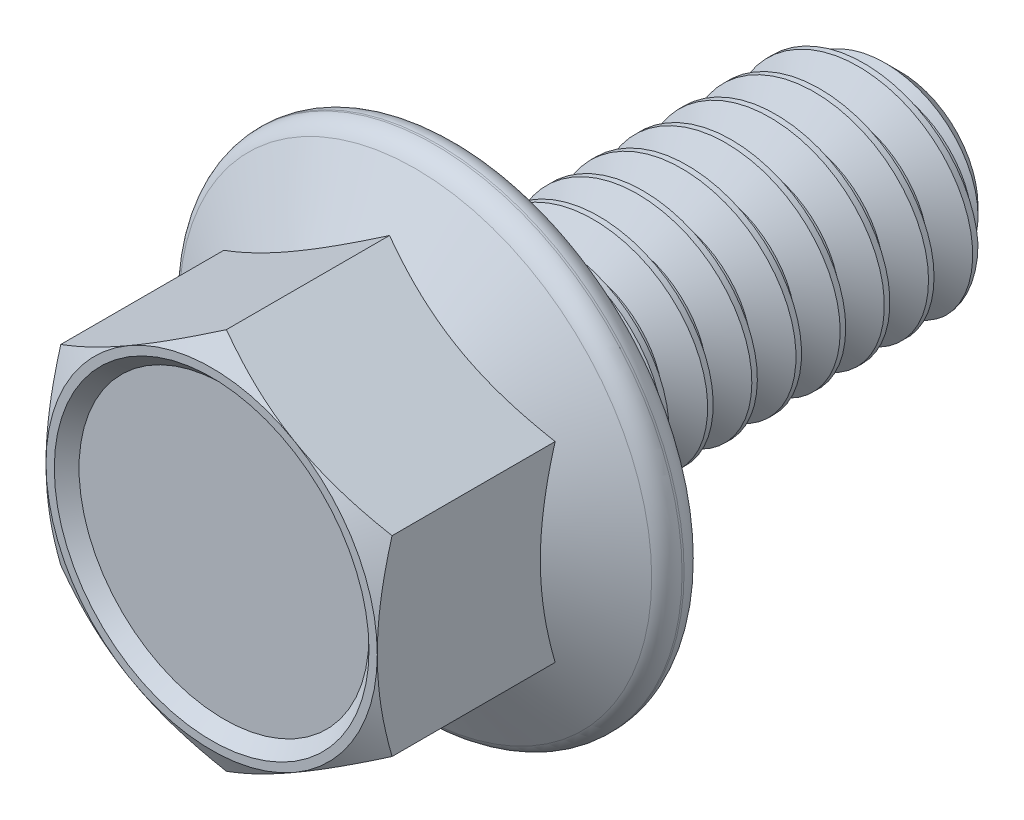
SolidWorks part; units mm, degrees
ref_plane "Front Plane" through (0, 0, 0) normal (0, 0, 1) x (1, 0, 0)
ref_plane "Top Plane" through (0, 0, 0) normal (0, 1, 0) x (1, 0, 0)
ref_plane "Right Plane" through (0, 0, 0) normal (1, 0, 0) x (0, 0, -1)
sketch "Sketch1" plane through (0, 0, 0) normal (1, 0, 0) x (0, 0, -1)
  line L0 (-9.906, 0) -> (9.906, 0) construction
  line L1 (9.8266, 3.3125) -> (10.4616, 2.2126) construction
  line L2 (10.4616, 2.2126) -> (11.0966, 3.3125) construction
  line L3 (11.0966, 3.3125) -> (9.8266, 3.3125) construction
  line L4 (9.906, 0) -> (9.906, 2.2225)
  line L5 (9.906, 2.2225) -> (8.9535, 3.175)
  line L6 (8.9535, 3.175) -> (-2.794, 3.175)
  line L7 (-2.794, 3.175) -> (-2.794, 7.112)
  line L8 (-2.794, 7.112) -> (-3.8608, 7.112)
  line L9 (8.9535, -3.175) -> (9.906, -2.2225) construction
  line L10 (-5.2173, 4.7625) -> (-9.906, 4.7625)
  line L11 (-9.906, 4.7625) -> (-9.906, 0)
  line L12 (8.9535, 3.175) -> (9.906, 3.175) construction
  line L13 (9.906, 3.175) -> (9.906, 2.2225) construction
  line L14 (10.4616, 2.2126) -> (10.4616, 2.3501) construction
  line L15 (-3.8608, 7.112) -> (-5.2173, 4.7625)
  line L16 (10.4616, 3.175) -> (10.4616, 3.3125) construction
  line L17 (9.8663, 3.2437) -> (11.0569, 3.2437) construction
  line L19 (11.0172, 3.175) -> (9.906, 3.175) construction
  line L21 (10.3822, 2.3501) -> (10.541, 2.3501) construction
  point P12 (6.731, 3.175)
  point P14 (10.4616, 3.2437)
  point P19 (6.731, -3.175)
  dimension "Screw Size Decimal Equivalent" = 6.35
  dimension "Flange Diameter" = 14.224
  dimension "Head Width" = 9.525
  dimension "Thread Pitch" = 1.27
  dimension "D1" = 0.1588
  dimension "D2" = 0.9525
  dimension "Length" = 12.7
  dimension "Head Height" = 7.112
  dimension "D3" = 1.0668
  dimension "D4" = 60
  dimension "D5" = 3.175
  dimension "Thread Size" = 6.35
sketch "Sketch2" plane through (0, 0, 0) normal (1, 0, 0) x (0, 0, -1)
  line L0 (-9.906, 0) -> (9.906, 0) construction
  line L1 (9.906, 0) -> (9.906, 2.2225) construction
  line L2 (9.906, 2.2225) -> (8.9535, 3.175) construction
  line L3 (8.9535, 3.175) -> (-2.794, 3.175) construction
  line L4 (-2.794, 3.175) -> (-2.794, 7.112) construction
  line L5 (-2.794, 7.112) -> (-3.8608, 7.112) construction
  line L6 (-3.8608, 7.112) -> (-5.2173, 4.7625) construction
  line L7 (-5.2173, 4.7625) -> (-9.906, 4.7625) construction
  line L8 (-9.906, 4.7625) -> (-9.906, 0) construction
  line L9 (-9.906, 0) -> (9.906, 0)
  line L10 (9.906, 0) -> (9.906, 2.2225)
  line L11 (9.906, 2.2225) -> (8.9535, 3.175)
  line L12 (8.9535, 3.175) -> (-2.794, 3.175)
  line L13 (-2.794, 3.175) -> (-2.794, 7.112)
  line L14 (-2.794, 7.112) -> (-3.8608, 7.112)
  line L15 (-3.8608, 7.112) -> (-5.2173, 4.7625)
  line L16 (-5.2173, 4.7625) -> (-9.906, 4.7625)
  line L17 (-9.906, 4.7625) -> (-9.906, 0)
revolve "Revolve1" add sketch "Sketch2" angle 360 about L9
sketch "Sketch3" plane through (0, 0, 9.906) normal (0, 0, 1) x (1, 0, 0)
  line L1 (0, 5.4993) -> (-4.7625, 2.7496)
  line L2 (-4.7625, 2.7496) -> (-4.7625, -2.7496)
  line L3 (-4.7625, -2.7496) -> (0, -5.4993)
  line L4 (0, -5.4993) -> (4.7625, -2.7496)
  line L5 (4.7625, -2.7496) -> (4.7625, 2.7496)
  line L6 (4.7625, 2.7496) -> (0, 5.4993)
  circle A0 centre (0, 0) radius 4.7625 construction
  circle A1 centre (0, 0) radius 4.7625 construction
extrude "Boss-Extrude1" add sketch "Sketch3" against normal up to surface (5.1141 mm away) up to face at (4.7625, 0, 5.2173)
sketch "Sketch4" plane through (0, 0, 9.906) normal (0, 0, 1) x (1, 0, 0)
  circle A0 centre (0, 0) radius 4.7625 construction
  circle A1 centre (0, 0) radius 4.7625
extrude "Cut-Extrude1" cut sketch "Sketch4" against normal through all draft 60 flip side to cut
sketch "Sketch10" plane through (0, 0, 9.906) normal (0, 0, 1) x (1, 0, 0)
  circle A0 centre (0, 0) radius 4.5244
  arc A1 (2.3812, 4.1244) -> (-2.3812, 4.1244) centre (0, 0) ccw construction
  dimension "D1" = 0.2381
extrude "Cut-Extrude2" cut sketch "Sketch10" against normal blind 0.3556 draft 45
fillet "Fillet1" radius 0.6401 2 edges at (7.112, 0, 2.794) (7.112, 0, 3.8608)
split "Split1" bodies to split 132 107 resulting bodies 108 109 split by face at (6.4719, 0, 2.794)
sketch "Sketch6" plane through (0, 0, -9.906) normal (0, 0, -1) x (-1, 0, 0)
  circle A0 centre (0, 0) radius 3.175 construction
  circle A1 centre (0, 0) radius 3.175
curve "Helix/Spiral1" pitch 1.27 height 16.51 radius 3.175 centre (0, 0, -9.906) axis (0, 0, 1) start towards (0, 1, 0)
sketch "Sketch7" plane through (0, 0, 0) normal (1, 0, 0) x (0, 0, -1)
  line L0 (9.8663, 3.2437) -> (10.3822, 2.3501)
  line L1 (10.3822, 2.3501) -> (10.541, 2.3501)
  line L2 (10.541, 2.3501) -> (11.0569, 3.2437)
  line L3 (11.0569, 3.2437) -> (9.8663, 3.2437)
sweep "Cut-Sweep1" cut profiles "Sketch7" path "Helix/Spiral1" align with end faces yes
combine bodies "Combine1" operation type add bodies to combine 110 109
sketch "Sketch8" plane through (0, 0, 2.794) normal (0, 0, -1) x (-1, 0, 0)
  circle A0 centre (0, 0) radius 3.175
extrude "Boss-Extrude2" add sketch "Sketch8" along normal blind 4.445 draft 20
equation "\"D1@Sketch1\" = \"Thread Pitch@Sketch1\" / 8"
equation "\"D2@Sketch1\" = .75 * \"Thread Pitch@Sketch1\""
equation "\"D3@Sketch1\"=\"Head Height@Sketch1\"*.15"
equation "\"D1@Fillet1\"=\"D3@Sketch1\"*.6"
equation "\"D3@Helix/Spiral1\" = \"Length@Sketch1\" + 3 * \"Thread Pitch@Sketch1\""
equation "\"D4@Helix/Spiral1\" = \"Thread Pitch@Sketch1\""
equation "\"D5@Sketch1\" = 2.5 * \"Thread Pitch@Sketch1\""
equation "\"D1@Boss-Extrude2\"=\"Thread Pitch@Sketch1\"*3.5"
equation "\"D1@Sketch10\"=\"Head Width@Sketch1\"/40"
equation "\"D1@Cut-Extrude2\"=\"Head Height@Sketch1\"/20"
